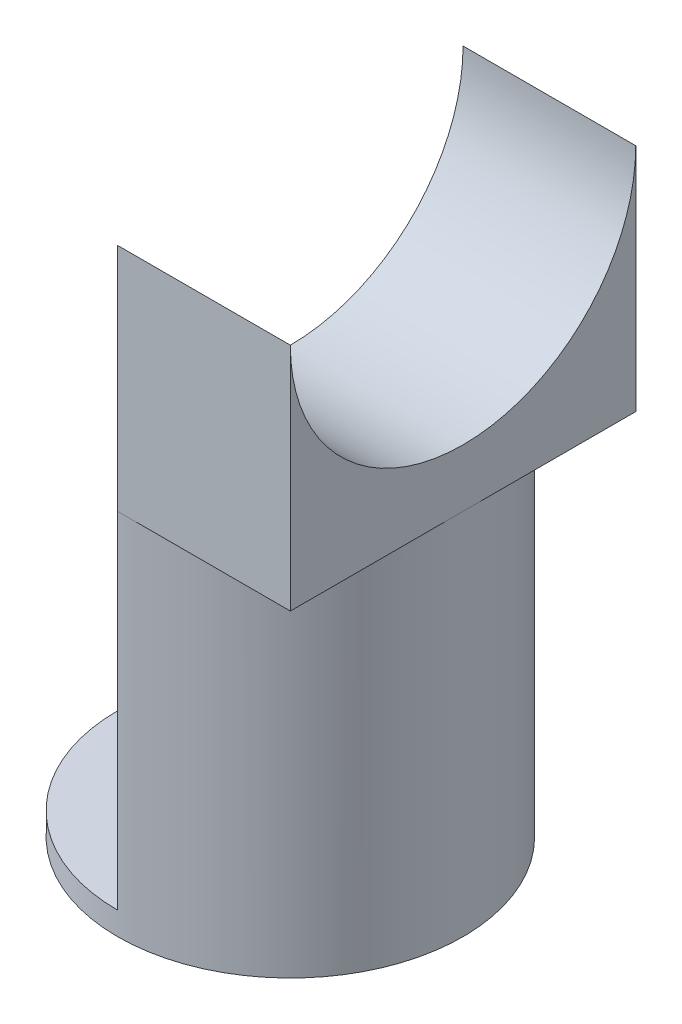
SolidWorks part; units mm, degrees
ref_plane "Front Plane" through (0, 0, 0) normal (0, 0, 1) x (1, 0, 0)
ref_plane "Top Plane" through (0, 0, 0) normal (0, 1, 0) x (1, 0, 0)
ref_plane "Right Plane" through (0, 0, 0) normal (1, 0, 0) x (0, 0, -1)
sketch "Sketch1" plane through (0, 0, 0) normal (0, 1, 0) x (1, 0, 0)
  circle A0 centre (0, 0) radius 75
  dimension "D1" = 150
extrude "Boss-Extrude1" add sketch "Sketch1" along normal blind 10
sketch "Sketch12" plane through (0, 10, 0) normal (0, 1, 0) x (1, 0, 0)
  line L0 (0, 0) -> (0, 75) construction
  line L1 (0, 75) -> (0, -75)
  circle A0 centre (0, 0) radius 75 construction
  arc A1 (0, -75) -> (0, 75) centre (0, 0) ccw
extrude "Boss-Extrude5" add sketch "Sketch12" along normal blind 150 contours L0 L1 region at (31.831, 10, 0)
sketch "Sketch13" plane through (0, 160, 0) normal (0, 1, 0) x (1, 0, 0)
  line L1 (0, 75) -> (75, 75)
  line L2 (0, 75) -> (0, -75)
  line L3 (0, -75) -> (75, -75)
  line L4 (75, 75) -> (75, -75)
extrude "Boss-Extrude6" add sketch "Sketch13" along normal blind 100
sketch "Sketch14" plane through (0, 0, 0) normal (-1, 0, 0) x (0, 0, 1)
  line L0 (-75, 260) -> (75, 260) construction
  circle A0 centre (0, 260) radius 75
extrude "Cut-Extrude5" cut sketch "Sketch14" against normal blind 100
